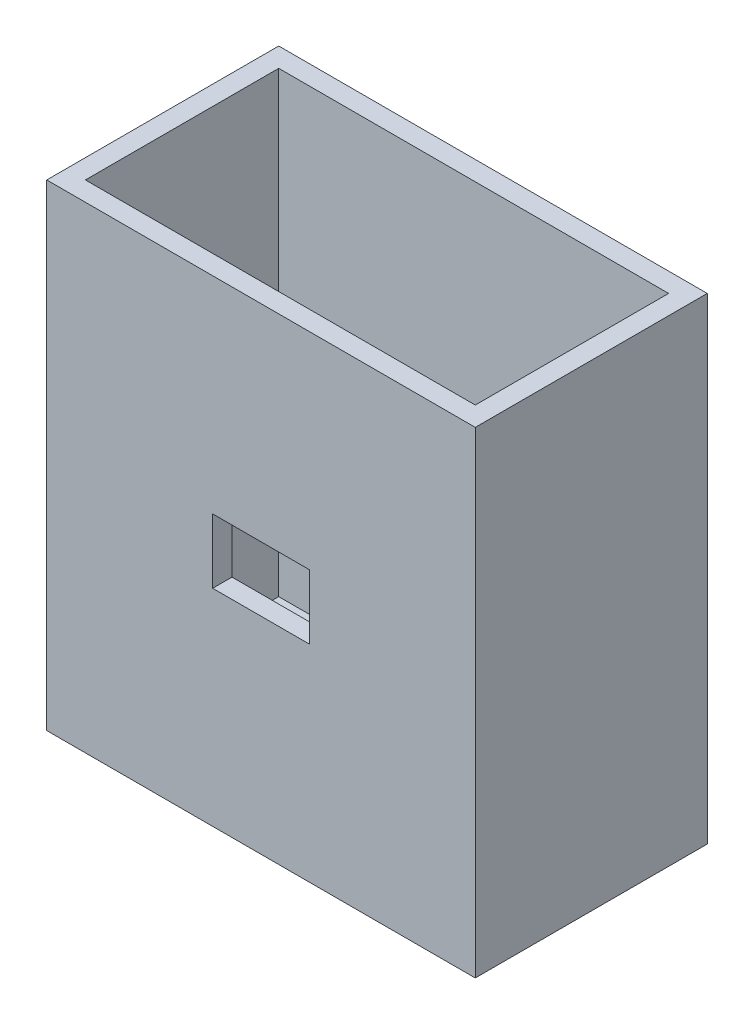
SolidWorks part; units mm, degrees
ref_plane "Front Plane" through (0, 0, 0) normal (0, 0, 1) x (1, 0, 0)
ref_plane "Top Plane" through (0, 0, 0) normal (0, 1, 0) x (1, 0, 0)
ref_plane "Right Plane" through (0, 0, 0) normal (1, 0, 0) x (0, 0, -1)
sketch "Sketch1" plane through (0, 0, 0) normal (0, 1, 0) x (1, 0, 0)
  line L0 (-33.25, 18) -> (33.25, 18)
  line L1 (-30.25, -15) -> (30.25, -15)
  line L2 (-30.25, -15) -> (-30.25, 15)
  line L3 (-30.25, 15) -> (30.25, 15)
  line L4 (30.25, -15) -> (30.25, 15)
  line L5 (-30.25, -15) -> (30.25, 15) construction
  line L6 (-30.25, 15) -> (30.25, -15) construction
  line L7 (33.25, -18) -> (33.25, 18)
  line L8 (-33.25, -18) -> (33.25, -18)
  line L9 (-33.25, -18) -> (-33.25, 18)
  point P0 (0, 0)
  dimension "D1" = 30
  dimension "D2" = 60.5
  dimension "D3" = 3
extrude "Boss-Extrude1" add sketch "Sketch1" along normal blind 71
extrude "Boss-Extrude2" add sketch "Sketch1<3>" against normal blind 3 contours L1 L4 L3 L2 | L9 L8 L7 L0 L4 L1 L2 L3 region at (0, 0, -17.2438) region at (0, 0, 0)
sketch "Sketch1<3>" plane through (0, 0, 0) normal (0, 1, 0) x (1, 0, 0) same geometry as "Sketch1"
sketch "Sketch2" plane through (0, 0, 18) normal (0, 0, 1) x (1, 0, 0)
  line L0 (0, 71) -> (0, -3) construction
  line L1 (-33.25, 71) -> (33.25, 71) construction
  line L2 (-33.25, -3) -> (33.25, -3) construction
  line L4 (7.5, 29) -> (-7.5, 29)
  line L5 (7.5, 29) -> (7.5, 39)
  line L6 (7.5, 39) -> (-7.5, 39)
  line L7 (-7.5, 29) -> (-7.5, 39)
  line L8 (7.5, 29) -> (-7.5, 39) construction
  line L9 (7.5, 39) -> (-7.5, 29) construction
  point P6 (0, 34)
  dimension "D1" = 15
  dimension "D2" = 10
extrude "Cut-Extrude1" cut sketch "Sketch2" against normal up to next
sketch "Sketch4" plane through (7.5, 0, 0) normal (-1, 0, 0) x (0, 0, 1)
  line L1 (15, 29) -> (14, 29)
  line L2 (15, 29) -> (15, 27)
  line L3 (15, 27) -> (14, 27)
  line L4 (14, 29) -> (14, 27)
  dimension "D1" = 1
  dimension "D2" = 2
extrude "Boss-Extrude4" add sketch "Sketch4" along normal up to surface (15 mm away) up to face at (-7.5, 34, 16.5)
chamfer "Chamfer1" distance 1 angle 45 1 edges at (0, 29, 14)
sketch "Sketch5" plane through (0, 0, -18) normal (0, 0, -1) x (-1, 0, 0)
  line L0 (33.25, 39) -> (-33.25, 39) construction
  line L1 (33.25, 71) -> (33.25, -3) construction
  line L2 (-33.25, 71) -> (-33.25, -3) construction
  text T0 "I" font "Times New Roman" height 10
  point P6 (33.25, 34)
  dimension "D1" = 5
extrude "Cut-Extrude2" cut sketch "Sketch5" against normal blind 1
